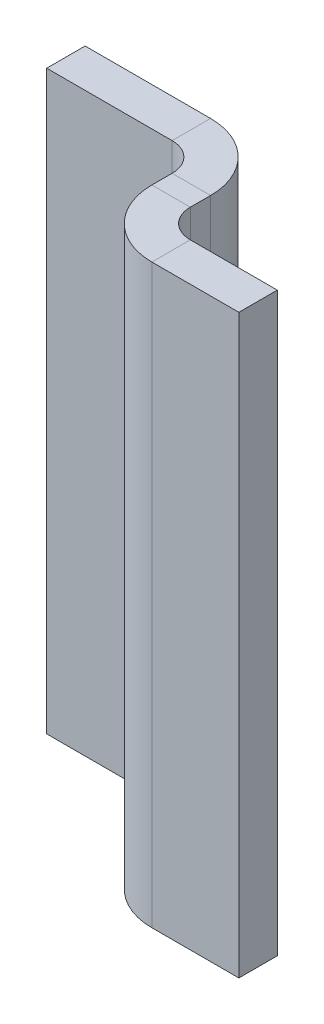
SolidWorks part; units mm, degrees
note: The reader was unsure of these and kept them because the rebuilt part matched: flange length of "Edge-Flange1", "Edge-Flange2".
material "Chrome Stainless Steel"
ref_plane "Front Plane" through (0, 0, 0) normal (0, 0, 1) x (1, 0, 0)
ref_plane "Top Plane" through (0, 0, 0) normal (0, 1, 0) x (1, 0, 0)
ref_plane "Right Plane" through (0, 0, 0) normal (1, 0, 0) x (0, 0, -1)
sketch "Sketch1" plane through (0, 0, 0) normal (0, 0, 1) x (1, 0, 0)
  line L1 (0, 0) -> (4, 0)
  line L2 (0, 0) -> (0, 15)
  line L3 (0, 15) -> (4, 15)
  line L4 (4, 0) -> (4, 15)
  dimension "D1" = 4
  dimension "D2" = 15
base flange "Base-Flange1" sketch "Sketch1" thickness 1 reverse thickness direction no parameters "D1"=0.7366
edge flange "Edge-Flange1" sketch "Sketch11" flange angle 90 flange length 3 flange position material outside bend radius 0.7366 thickness 1 relief rectangular parameters "D6"=10
sketch "Sketch11" plane through (4, 0, 0) normal (1, 0, 0) x (0, 1, 0)
  line L0 (0, 0) -> (15, 0) construction
  line L1 (0, 0) -> (15, 0)
  line L2 (0, 0) -> (0, 2)
  line L3 (0, 2) -> (15, 2)
  line L4 (15, 2) -> (15, 0)
bend "EdgeBend1" bend radius 0.7366 bend angle 90 parameters "D5"=1
edge flange "Edge-Flange2" sketch "Sketch14" flange angle 90 flange length 4 flange position material outside bend radius 0.7366 thickness 1 relief rectangular parameters "D6"=10
sketch "Sketch14" plane through (5, 0, 2) normal (0, 0, 1) x (0, -1, 0)
  line L2 (-15, 0) -> (-15, 3)
  line L3 (-15, 3) -> (0, 3)
  line L4 (0, 3) -> (0, 0)
  line L5 (-15, 0) -> (0, 0) construction
  line L6 (-15, 0) -> (0, 0)
bend "EdgeBend2" bend radius 0.7366 bend angle 90 parameters "D5"=2
sketch "Bend-Lines1" [suppressed] plane through (0, 0, 0) normal (0, 1, 0) x (1, 0, 0)
sketch "Bounding-Box1" [suppressed] plane through (0, 0, 0) normal (0, 1, 0) x (1, 0, 0)
sheet metal parameters "Sheet-Metal1" thickness 1 parameters "D1"=0.7366
flat pattern "Flat-Pattern1" [suppressed]
sketch "Bend-Lines2" plane through (0, 0, 0) normal (0, 1, 0) x (1, 0, 0)
sketch3d "Bounding-Box2" [suppressed]
  line L0 (4, 15, 0) -> (4, 0, 0) construction
  line L1 (0, 15, 0) -> (0, 0, 0) construction
  line L2 (4, 15, 0) -> (0, 15, 0) construction
  line L3 (4, 0, 0) -> (0, 0, 0) construction
sheet metal parameters "Sheet-Metal2" thickness 1 parameters "D1"=0.7366
flat pattern "Flat-Pattern1"
sketch "Bend-Lines2" plane through (0, 0, 0) normal (0, 0, 1) x (1, 0, 0)
  line L0 (4.2346, 0) -> (4.2346, 15) construction
  line L1 (4.2346, 0) -> (4.2346, 15) construction
sketch3d "Bounding-Box2" [suppressed]
  line L0 (7.4692, 15, 0) -> (7.4692, 0, 0) construction
  line L1 (0, 15, 0) -> (0, 0, 0) construction
  line L2 (7.4692, 15, 0) -> (0, 15, 0) construction
  line L3 (7.4692, 0, 0) -> (0, 0, 0) construction
bend of the flat pattern "Flatten-<EdgeBend1>1"
sheet metal parameters "Sheet-Metal3" thickness 1 parameters "D1"=0.7366
flat pattern "Flat-Pattern1"
sketch "Bend-Lines2" plane through (0, 0, 0) normal (0, 0, 1) x (1, 0, 0)
  line L0 (4.2346, 0) -> (4.2346, 15) construction
  line L1 (4.2346, 0) -> (4.2346, 15) construction
  line L2 (6.7039, 0) -> (6.7039, 15) construction
  line L3 (6.7039, 0) -> (6.7039, 15) construction
sketch3d "Bounding-Box2" [suppressed]
  line L0 (9.9385, 15, 0) -> (9.9385, 0, 0) construction
  line L1 (0, 15, 0) -> (0, 0, 0) construction
  line L2 (9.9385, 15, 0) -> (0, 15, 0) construction
  line L3 (9.9385, 0, 0) -> (0, 0, 0) construction
bend of the flat pattern "Flatten-<EdgeBend1>1"
bend of the flat pattern "Flatten-<EdgeBend2>1"
